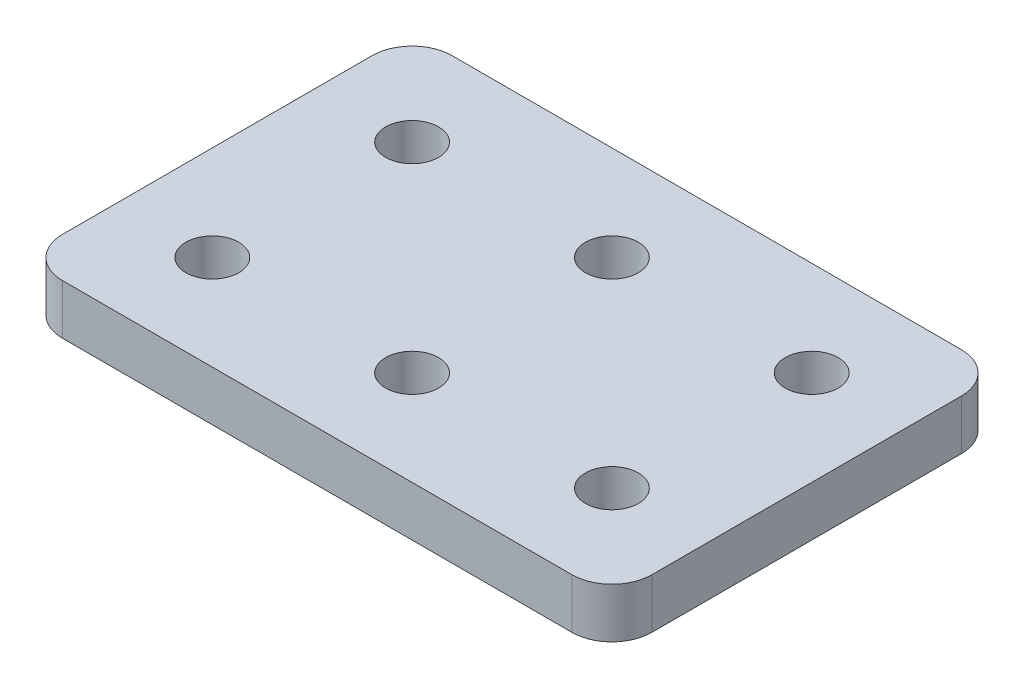
SolidWorks part; units mm, degrees
ref_plane "Top" through (0, 0, 0) normal (0, 0, 1) x (1, 0, 0)
ref_plane "Front" through (0, 0, 0) normal (0, 1, 0) x (1, 0, 0)
ref_plane "Right" through (0, 0, 0) normal (1, 0, 0) x (0, 0, -1)
sketch "2 Hole Profile Sketch" [suppressed] plane through (0, 0, 0) normal (0, 1, 0) x (1, 0, 0)
  line L0 (0, -10) -> (0, 10) construction
  line L1 (-16.5, -9.5) -> (16.5, -9.5)
  line L2 (-19.5, -6.5) -> (-19.5, 6.5)
  line L3 (-16.5, 9.5) -> (16.5, 9.5)
  line L4 (19.5, -6.5) -> (19.5, 6.5)
  line L5 (-20, -10) -> (20, -10) construction
  line L6 (-20, -10) -> (-20, 10) construction
  line L7 (-20, 10) -> (20, 10) construction
  line L8 (20, -10) -> (20, 10) construction
  arc A0 (-16.5, -9.5) -> (-19.5, -6.5) centre (-16.5, -6.5) cw
  arc A1 (-16.5, 9.5) -> (-19.5, 6.5) centre (-16.5, 6.5) ccw
  arc A2 (19.5, 6.5) -> (16.5, 9.5) centre (16.5, 6.5) ccw
  arc A3 (16.5, -9.5) -> (19.5, -6.5) centre (16.5, -6.5) ccw
  circle A4 centre (-10, 0) radius 2.65
  circle A5 centre (10, 0) radius 2.65
  point P24 (0, 0)
  dimension "D2" = 0.5
  dimension "D3" = 0.5
  dimension "D4" = 0.5
  dimension "D7" = 10
  dimension "D1" = 3
  dimension "D5" = 0.5
  dimension "D6" = 20
  dimension "D9" = 10
  dimension "D12" = 20
  dimension "D8" = 5.3
  dimension "D11" = 20
extrude "2 Hole Profile" [suppressed] add sketch "2 Hole Profile Sketch" along normal blind 5
sketch "3 Hole Profile Sketch" plane through (0, 0, 0) normal (0, 1, 0) x (1, 0, 0)
  line L0 (0, -10) -> (0, 10) construction
  line L1 (-16.5, -9.5) -> (36.5, -9.5)
  line L2 (-19.5, -6.5) -> (-19.5, 6.5)
  line L3 (-16.5, 9.5) -> (36.5, 9.5)
  line L4 (39.5, -6.5) -> (39.5, 6.5)
  line L5 (-20, -10) -> (40, -10) construction
  line L6 (-20, -10) -> (-20, 10) construction
  line L7 (-20, 10) -> (40, 10) construction
  line L8 (40, -10) -> (40, 10) construction
  arc A0 (-16.5, -9.5) -> (-19.5, -6.5) centre (-16.5, -6.5) cw
  arc A1 (-16.5, 9.5) -> (-19.5, 6.5) centre (-16.5, 6.5) ccw
  arc A2 (39.5, 6.5) -> (36.5, 9.5) centre (36.5, 6.5) ccw
  arc A3 (36.5, -9.5) -> (39.5, -6.5) centre (36.5, -6.5) ccw
  circle A4 centre (-10, 0) radius 2.65
  circle A5 centre (10, 0) radius 2.65
  circle A6 centre (30, 0) radius 2.65
  point P29 (0, 0)
  dimension "D2" = 0.5
  dimension "D3" = 0.5
  dimension "D4" = 0.5
  dimension "D10" = 20
  dimension "D7" = 10
  dimension "D1" = 3
  dimension "D8" = 5.3
  dimension "D5" = 0.5
  dimension "D6" = 20
  dimension "D9" = 10
  dimension "D11" = 40
  dimension "D12" = 20
extrude "3 Hole Thickness Extrude" [suppressed] add sketch "3 Hole Profile Sketch" along normal blind 5
sketch "4 Hole Profile Sketch" plane through (0, 0, 0) normal (0, 1, 0) x (1, 0, 0)
  line L1 (-15.5, -19.5) -> (15.5, -19.5)
  line L2 (-19.5, -15.5) -> (-19.5, 15.5)
  line L3 (-15.5, 19.5) -> (15.5, 19.5)
  line L4 (19.5, -15.5) -> (19.5, 15.5)
  line L5 (0, 19.5) -> (0, -19.5) construction
  line L6 (-19.5, 0) -> (19.5, 0) construction
  line L7 (-20, 20) -> (20, 20) construction
  line L8 (-20, 20) -> (-20, -20) construction
  line L9 (-20, -20) -> (20, -20) construction
  line L10 (20, 20) -> (20, -20) construction
  line L11 (-20, 20) -> (20, -20) construction
  line L12 (-20, -20) -> (20, 20) construction
  circle A0 centre (10, -10) radius 2.65
  circle A1 centre (10, 10) radius 2.65
  circle A2 centre (-10, -10) radius 2.65
  circle A3 centre (-10, 10) radius 2.65
  arc A4 (-19.5, -15.5) -> (-15.5, -19.5) centre (-15.5, -15.5) ccw
  arc A5 (19.5, -15.5) -> (15.5, -19.5) centre (15.5, -15.5) cw
  arc A6 (15.5, 19.5) -> (19.5, 15.5) centre (15.5, 15.5) cw
  arc A7 (-19.5, 15.5) -> (-15.5, 19.5) centre (-15.5, 15.5) cw
  point P14 (0, 0)
  point P22 (-25, -26)
  point P144 (0, 0)
  dimension "Corner Radius" = 4
  dimension "D9" = 5.3
  dimension "D5" = 10
  dimension "D6" = 10
  dimension "D7" = 10
  dimension "D1" = 40
  dimension "D2" = 0.5
  dimension "D3" = 0.5
  dimension "D4" = 0.5
  dimension "D10" = 20
  dimension "D8" = 10
extrude "4 Hole Thickness Extrude" add sketch "4 Hole Profile Sketch" along normal blind 5
sketch "6 Hole Extension Sketch" plane through (0, 0, 0) normal (0, 1, 0) x (1, 0, 0)
  line L0 (39.5, -15.5) -> (39.5, 15.5)
  line L1 (-20, -19.5) -> (15.5, -19.5) construction
  line L2 (-20, -19.5) -> (-20, 19.5) construction
  line L3 (-20, 19.5) -> (15.5, 19.5) construction
  line L4 (19.5, -15.5) -> (19.5, 15.5)
  line L5 (0, 19.5) -> (0, -19.5) construction
  line L6 (-20, 0) -> (19.5, 0) construction
  line L7 (15.5, -19.5) -> (35.5, -19.5)
  line L8 (15.5, 19.5) -> (35.5, 19.5)
  arc A8 (39.5, -15.5) -> (35.5, -19.5) centre (35.5, -15.5) cw
  arc A9 (35.5, 19.5) -> (39.5, 15.5) centre (35.5, 15.5) cw
  arc A10 (19.5, -15.5) -> (15.5, -19.5) centre (15.5, -15.5) cw
  arc A11 (19.5, 15.5) -> (15.5, 19.5) centre (15.5, 15.5) ccw
  circle A12 centre (30, -10) radius 2.65
  circle A13 centre (30, 10) radius 2.65
  point P18 (-22.5, -23)
  point P27 (0, 0)
  dimension "Corner Radius" = 4
  dimension "D5" = 5.3
  dimension "D1" = 19.5
  dimension "D2" = 20
  dimension "D6" = 39
  dimension "D7" = 10
  dimension "D8" = 20
  dimension "D3" = 30
  dimension "D4" = 39.5
extrude "6 Hole Extension Extrude" add sketch "6 Hole Extension Sketch" along normal up to surface (5 mm away) up to face at (-10, 5, 12.65)
equation "\"M5 Close Fit Hole\"= 5.3mm"
equation "\"D9@4 Hole Profile Sketch\" = \"M5 Close Fit Hole\""
equation "\"D5@6 Hole Extension Sketch\" = \"M5 Close Fit Hole\""
equation "\"Clearance\"= 0.5mm"
equation "\"D2@4 Hole Profile Sketch\"=\"Clearance\""
equation "\"D3@4 Hole Profile Sketch\"=\"Clearance\""
equation "\"D4@4 Hole Profile Sketch\"=\"Clearance\""
equation "\"D6@6 Hole Extension Sketch\"=40-2*\"Clearance\""
equation "\"D1@6 Hole Extension Sketch\"=20-\"Clearance\""
equation "\"D2@3 Hole Profile Sketch\" = \"Clearance\""
equation "\"D3@3 Hole Profile Sketch\" = \"Clearance\""
equation "\"D4@3 Hole Profile Sketch\" = \"Clearance\""
equation "\"D5@3 Hole Profile Sketch\" = \"Clearance\""
equation "\"D8@3 Hole Profile Sketch\" = \"M5 Close Fit Hole\""
equation "\"Plate Thickness\"= 5"
equation "\"D1@4 Hole Thickness Extrude\"=\"Plate Thickness\""
equation "\"D1@3 Hole Thickness Extrude\"=\"Plate Thickness\""
equation "\"D8@2 Hole Profile Sketch\" = \"M5 Close Fit Hole\""
equation "\"D1@2 Hole Profile\" = \"Plate Thickness\""
